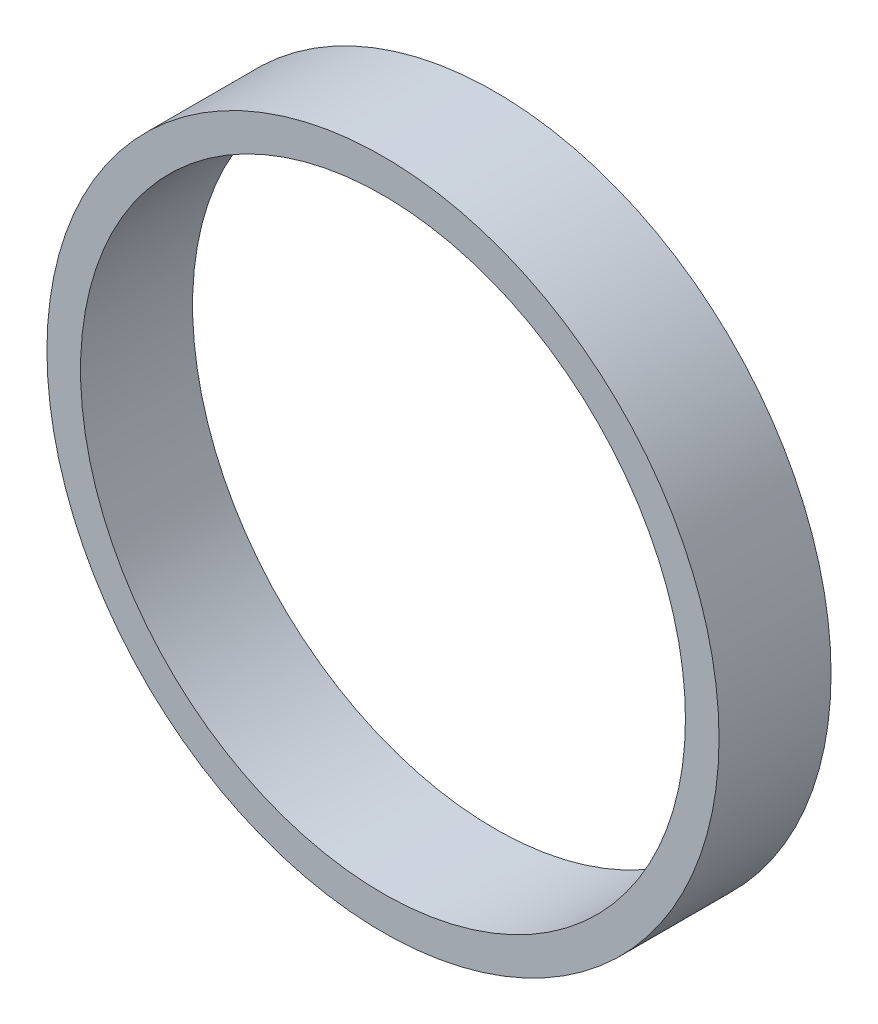
SolidWorks part; units mm, degrees
ref_plane "前视基准面" through (0, 0, 0) normal (0, 0, 1) x (1, 0, 0)
ref_plane "上视基准面" through (0, 0, 0) normal (0, 1, 0) x (1, 0, 0)
ref_plane "右视基准面" through (0, 0, 0) normal (1, 0, 0) x (0, 0, -1)
other "Configuration Table"
sketch "Sketch1" plane through (0, 0, 0) normal (0, 0, 1) x (1, 0, 0)
  circle A0 centre (0, 0) radius 60
  circle A1 centre (0, 0) radius 54
extrude "Boss-Extrude1" add sketch "Sketch1" along normal blind 20
ref_plane "bottom_face" through (0, 0, 0) normal (0, 0, 1) x (1, 0, 0)
sketch3d "3DSketch1"
  line L0 (0, 0, 0) -> (0, 0, 20) construction
ref_axis "center_axis" through (0, 0, 0) along (0, 0, 1)
